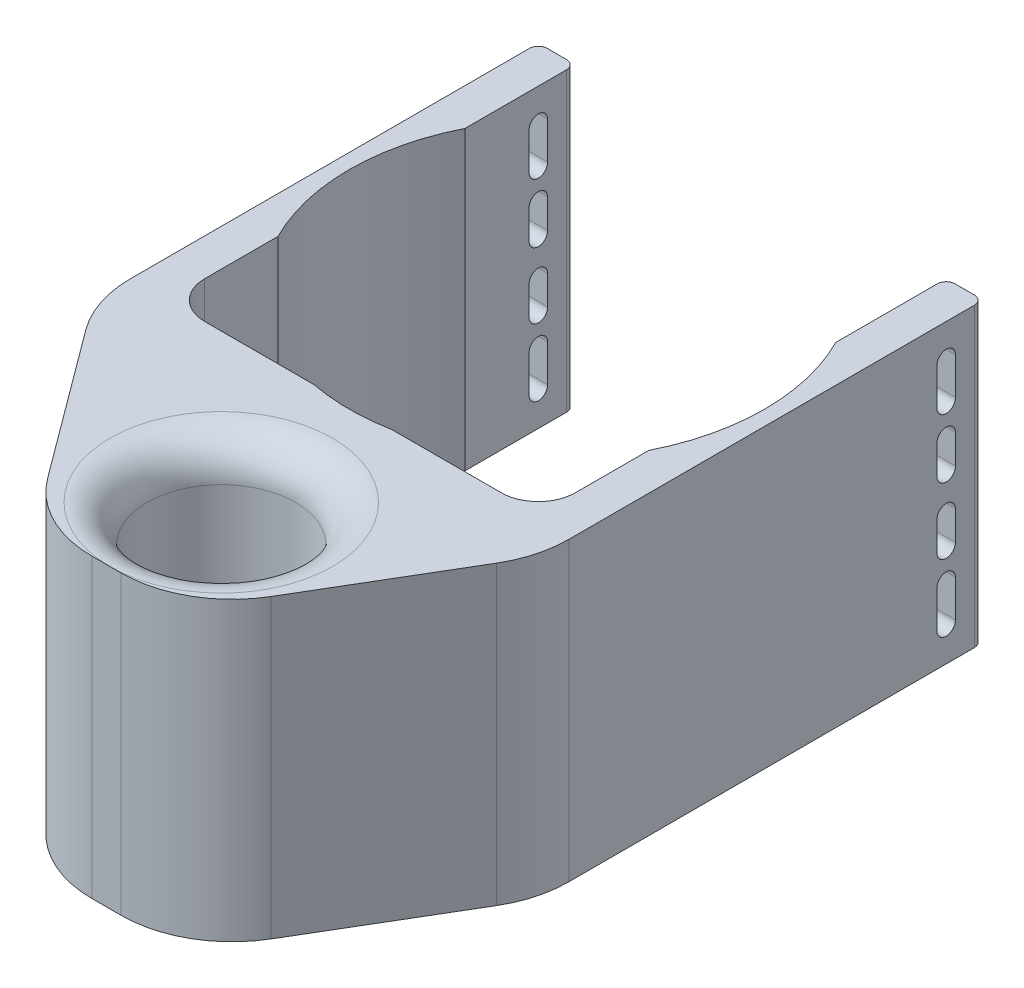
SolidWorks part; units mm, degrees
ref_plane "Front Plane" through (0, 0, 0) normal (0, 0, 1) x (1, 0, 0)
ref_plane "Top Plane" through (0, 0, 0) normal (0, 1, 0) x (1, 0, 0)
ref_plane "Right Plane" through (0, 0, 0) normal (1, 0, 0) x (0, 0, -1)
sketch "Sketch1" plane through (0, 0, 0) normal (0, 1, 0) x (1, 0, 0)
  line L0 (6.35, 0) -> (57.15, 0)
  line L1 (63.5, 6.35) -> (63.5, 68.326)
  line L2 (0, 6.35) -> (0, 68.326)
  line L3 (69.85, -1.1339) -> (69.85, 68.326)
  line L5 (-6.35, -0.0589) -> (-6.35, 68.326)
  line L6 (-4.826, 69.85) -> (-1.524, 69.85)
  line L7 (65.024, 69.85) -> (68.326, 69.85)
  line L8 (63.5, 0) -> (63.5, 63.5) construction
  line L9 (69.85, -6.35) -> (69.85, 63.5) construction
  line L10 (-6.35, -6.35) -> (-6.35, 63.5) construction
  line L11 (0, 0) -> (0, 63.5) construction
  line L12 (0, 0) -> (63.5, 0) construction
  line L16 (52.8273, -35.1045) -> (67.1928, -10.8385)
  line L17 (36.4345, -44.45) -> (31.4862, -44.45)
  line L18 (16.1828, -36.7449) -> (-2.6034, -11.4038)
  line L20 (-6.35, -6.35) -> (69.85, -6.35) construction
  arc A0 (63.5, 68.326) -> (65.024, 69.85) centre (65.024, 68.326) cw
  arc A1 (69.85, 68.326) -> (68.326, 69.85) centre (68.326, 68.326) ccw
  arc A2 (-6.35, 68.326) -> (-4.826, 69.85) centre (-4.826, 68.326) cw
  arc A3 (0, 68.326) -> (-1.524, 69.85) centre (-1.524, 68.326) ccw
  circle A4 centre (34.5948, -25.4) radius 12.7
  arc A5 (36.4345, -44.45) -> (52.8273, -35.1045) centre (36.4345, -25.4) ccw
  arc A6 (31.4862, -44.45) -> (16.1828, -36.7449) centre (31.4862, -25.4) cw
  arc A7 (69.85, -1.1339) -> (67.1928, -10.8385) centre (50.8, -1.1339) cw
  arc A8 (-2.6034, -11.4038) -> (-6.35, -0.0589) centre (12.7, -0.0589) cw
  arc A9 (57.15, 0) -> (63.5, 6.35) centre (57.15, 6.35) ccw
  arc A10 (6.35, 0) -> (0, 6.35) centre (6.35, 6.35) cw
  point P21 (48.0325, -44.45)
  point P30 (0, 0)
  dimension "D3" = 1.524
  dimension "D6" = 19.05
  dimension "D7" = 19.05
  dimension "D8" = 6.35
  dimension "D2" = 6.35
extrude "Boss-Extrude1" add sketch "Sketch1" along normal mid plane 50.8
sketch "Sketch2" plane through (0, 25.4, 0) normal (0, 1, 0) x (1, 0, 0)
  circle A0 centre (31.75, 34.925) radius 35.56
extrude "Cut-Extrude1" cut sketch "Sketch2" against normal blind 50.8
sketch "Sketch3" plane through (69.85, 0, 0) normal (1, 0, 0) x (0, 0, -1)
  line L2 (63.5, -3.175) -> (63.5, -8.1497) construction
  line L3 (63.5, -3.175) -> (63.5, -9.525)
  line L4 (65.0875, -3.175) -> (65.0875, -8.1497)
  line L5 (63.5, -13.335) -> (63.5, -19.685)
  line L6 (61.9125, -3.175) -> (61.9125, -8.1497)
  line L7 (63.5, -13.335) -> (63.5, -19.685) construction
  line L8 (65.0875, -13.335) -> (65.0875, -19.685)
  line L9 (61.9125, -13.335) -> (61.9125, -19.685)
  line L10 (63.5, 13.335) -> (63.5, 19.685) construction
  line L11 (65.0875, 13.335) -> (65.0875, 19.685)
  line L12 (61.9125, 13.335) -> (61.9125, 19.685)
  line L13 (63.5, 3.175) -> (63.5, 8.1497) construction
  line L14 (65.0875, 3.175) -> (65.0875, 8.1497)
  line L15 (61.9125, 3.175) -> (61.9125, 8.1497)
  arc A0 (65.0875, -3.175) -> (61.9125, -3.175) centre (63.5, -3.175) ccw
  arc A1 (61.9125, -8.1497) -> (65.0875, -8.1497) centre (63.5, -8.1497) ccw
  arc A2 (65.0875, -13.335) -> (61.9125, -13.335) centre (63.5, -13.335) ccw
  arc A3 (61.9125, -19.685) -> (65.0875, -19.685) centre (63.5, -19.685) ccw
  arc A4 (65.0875, 13.335) -> (61.9125, 13.335) centre (63.5, 13.335) cw
  arc A5 (61.9125, 19.685) -> (65.0875, 19.685) centre (63.5, 19.685) cw
  arc A6 (65.0875, 3.175) -> (61.9125, 3.175) centre (63.5, 3.175) cw
  arc A7 (61.9125, 8.1497) -> (65.0875, 8.1497) centre (63.5, 8.1497) cw
  point P9 (63.5, -5.6623)
  point P15 (63.5, -16.51)
  point P22 (63.5, 16.51)
  point P29 (63.5, 5.6623)
  dimension "D2" = 6.35
  dimension "D3" = 3.81
  dimension "D4" = 6.35
extrude "Cut-Extrude2" cut sketch "Sketch3" against normal blind 127 contours A5 L12 A4 L11 | L9 A3 L8 A2 | L14 A7 L15 A6 | L4 A1 L6 A0 region at (69.85, -16.51, -64.9871) region at (69.85, 16.51, -63.5)
fillet "Fillet1" radius 6.35 2 edges at (34.5948, -25.4, 38.1) (34.5948, 25.4, 38.1)
